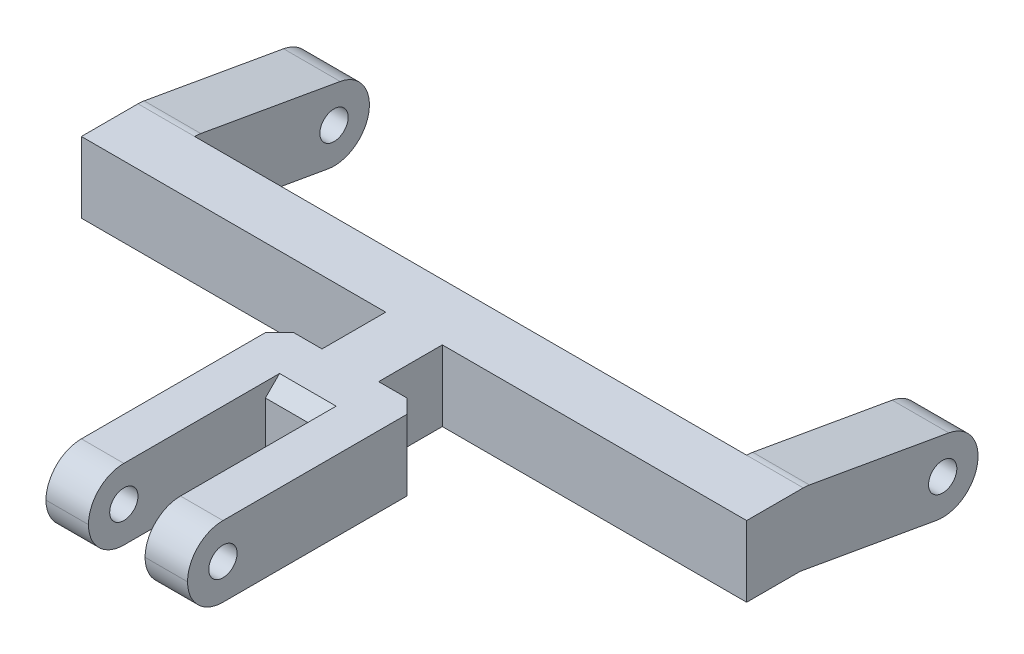
SolidWorks part; units mm, degrees
material "1060 合金"
ref_plane "前视基准面" through (0, 0, 0) normal (0, 0, 1) x (1, 0, 0)
ref_plane "上视基准面" through (0, 0, 0) normal (0, 1, 0) x (1, 0, 0)
ref_plane "右视基准面" through (0, 0, 0) normal (1, 0, 0) x (0, 0, -1)
sketch "草图1" plane through (0, 0, 0) normal (0, 1, 0) x (1, 0, 0)
  line L0 (0, 73.9355) -> (0, -76) construction
  line L5 (-4, -50) -> (-10, -50)
  line L9 (-47, 0) -> (47, 0)
  line L23 (47, -8) -> (4, -8)
  line L27 (-4, -50) -> (-4, -25)
  line L29 (-10, -50) -> (-10, -17)
  line L32 (10, -50) -> (10, -17)
  line L34 (4, -50) -> (4, -25)
  line L39 (4, -50) -> (10, -50)
  line L41 (-10, -17) -> (-4, -17)
  line L42 (4, -25) -> (-4, -25)
  line L43 (-4, -17) -> (-4, -8)
  line L44 (4, -17) -> (4, -8)
  line L45 (4, -17) -> (10, -17)
  line L46 (-4, -8) -> (-47, -8)
  line L47 (-47, -8) -> (-47, 0)
  line L48 (47, -8) -> (47, 0)
  point P19 (0, -19)
  point P20 (0, 19)
  point P21 (0, 0)
  point P23 (0, 2)
  point P24 (0, 0)
  point P27 (0, -15)
  point P28 (0, -70)
  point P30 (0, -7)
  dimension "D1" = 8
  dimension "D2" = 94
  dimension "D3" = 50
  dimension "D4" = 8
  dimension "D6" = 6
  dimension "D9" = 4
  dimension "D10" = 25
  dimension "D11" = 8
extrude "凸台-拉伸1" add sketch "草图1" along normal blind 10
fillet "圆角1" radius 5 4 edges at (-7, 0, 50) (-7, 10, 50) (7, 10, 50) (7, 0, 50)
sketch "草图6" plane through (0, 0, 0) normal (1, 0, 0) x (0, 0, -1)
  line L0 (0, 10) -> (0, 0) construction
  line L1 (0.8682, 9.924) -> (20.5644, 6.4511)
  line L2 (-0.8682, 0.076) -> (18.8279, -3.397)
  line L4 (-8, 0) -> (0, 0) construction
  arc A0 (0.8682, 9.924) -> (-0.8682, 0.076) centre (0, 5) ccw
  arc A1 (18.8279, -3.397) -> (20.5644, 6.4511) centre (19.6962, 1.527) ccw
  circle A2 centre (19.6962, 1.527) radius 2
  dimension "D3" = 4
  dimension "D1" = 10
  dimension "D2" = 20
extrude "凸台-拉伸2" add sketch "草图6" against normal blind 8 from surface starting at face at (47, 5, 4)
extrude "凸台-拉伸3" add sketch "草图6<2>" along normal blind 8 from surface starting at face at (-47, 5, 4)
sketch "草图6<2>" plane through (0, 0, 0) normal (1, 0, 0) x (0, 0, -1) same geometry as "草图6"
sketch "草图7" plane through (0, 0, 0) normal (1, 0, 0) x (0, 0, -1)
  circle A0 centre (-45, 5) radius 2
  dimension "D1" = 4
extrude "切除-拉伸4" cut sketch "草图7" against normal through all both and the other way through all
chamfer "倒角1" distance 2 angle 45 2 edges at (0, 0, 25) (0, 10, 25)
chamfer "倒角2" distance 2 angle 45 2 edges at (-10, 5, 17) (10, 5, 17)
